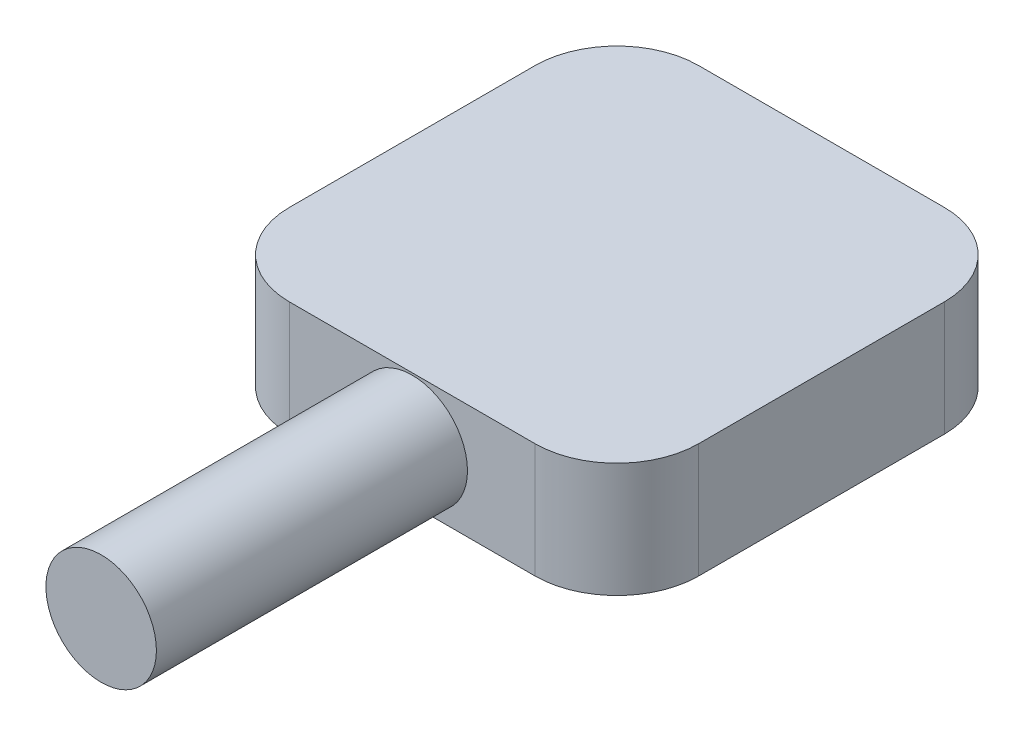
SolidWorks part; units mm, degrees
material "6061 Alloy"
ref_plane "Front Plane" through (0, 0, 0) normal (0, 0, 1) x (1, 0, 0)
ref_plane "Top Plane" through (0, 0, 0) normal (0, 1, 0) x (1, 0, 0)
ref_plane "Right Plane" through (0, 0, 0) normal (1, 0, 0) x (0, 0, -1)
sketch "Sketch1" plane through (0, 0, 0) normal (0, 0, 1) x (1, 0, 0)
  circle A0 centre (0, 0) radius 6.75
  dimension "D1" = 13.5
extrude "Boss-Extrude1" add sketch "Sketch1" along normal blind 10 and the other way blind 73
sketch "Sketch2" plane through (0, 0, 0) normal (0, 1, 0) x (-1, 0, 0)
  line L1 (-15, -78) -> (15, -78)
  line L2 (-25, -68) -> (-25, -38)
  line L3 (-15, -28) -> (15, -28)
  line L4 (25, -68) -> (25, -38)
  arc A0 (15, -28) -> (25, -38) centre (15, -38) cw
  arc A1 (25, -68) -> (15, -78) centre (15, -68) cw
  arc A2 (-25, -38) -> (-15, -28) centre (-15, -38) cw
  arc A3 (-25, -68) -> (-15, -78) centre (-15, -68) ccw
  point P4 (25, -53)
  point P6 (0, -78)
  point P11 (25, -78)
  point P16 (-25, -78)
  dimension "D3" = 10
  dimension "D1" = 53
  dimension "D2" = 50
  dimension "D4" = 50
extrude "Boss-Extrude2" add sketch "Sketch2" along normal blind 7 and the other way blind 7
